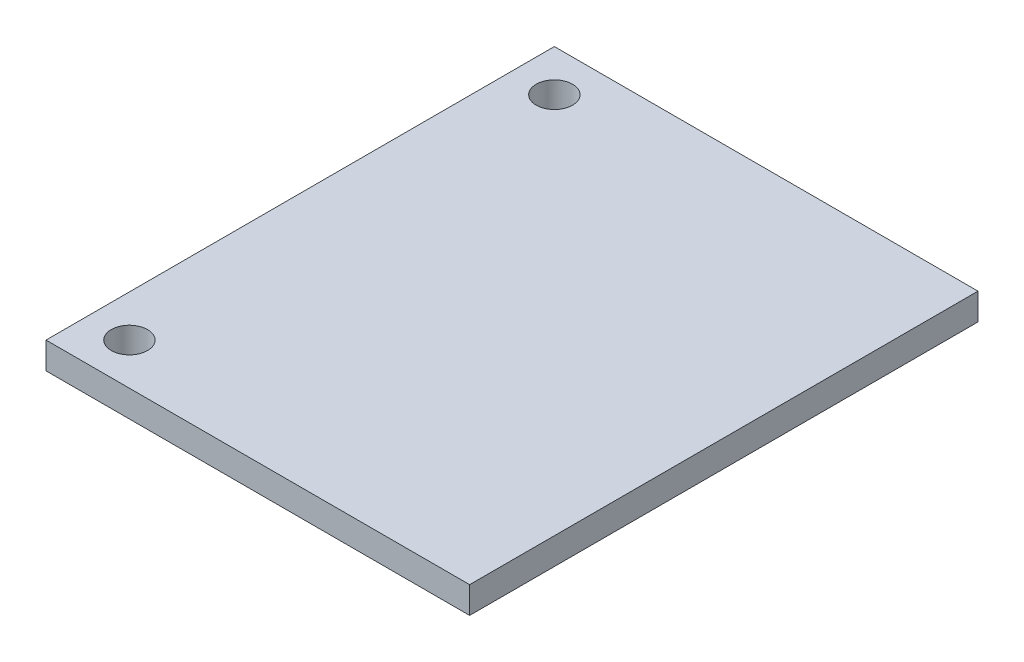
SolidWorks part; units mm, degrees
ref_plane "Front" through (0, 0, 0) normal (0, 0, 1) x (1, 0, 0)
ref_plane "Top" through (0, 0, 0) normal (0, 1, 0) x (1, 0, 0)
ref_plane "Right" through (0, 0, 0) normal (1, 0, 0) x (0, 0, -1)
sketch "Sketch1" plane through (0, 0, 0) normal (0, 1, 0) x (1, 0, 0)
  line L1 (-12.7, 15.24) -> (12.7, 15.24)
  line L2 (-12.7, 15.24) -> (-12.7, -15.24)
  line L3 (-12.7, -15.24) -> (12.7, -15.24)
  line L4 (12.7, 15.24) -> (12.7, -15.24)
  line L5 (-12.7, 15.24) -> (12.7, -15.24) construction
  line L6 (-12.7, -15.24) -> (12.7, 15.24) construction
  point P0 (0, 0)
  dimension "D1" = 25.4
  dimension "D2" = 30.48
extrude "Boss-Extrude1" add sketch "Sketch1" along normal blind 1.6
sketch "Sketch2" plane through (0, 1.6, 0) normal (0, 1, 0) x (1, 0, 0)
  line L0 (-12.7, 15.24) -> (-12.7, -15.24) construction
  line L2 (12.7, 15.24) -> (-12.7, 15.24) construction
  circle A0 centre (-10.2, 12.74) radius 1.09
  point P6 (-11.0474, 15.24)
  dimension "D1" = 2.18
  dimension "D2" = 2.5
  dimension "D3" = 2.5
extrude "Cut-Extrude1" cut sketch "Sketch2" against normal blind 1.6
mirror "Mirror1" about plane through (0, 0, 0) normal (0, 0, 1) of "Cut-Extrude1"
